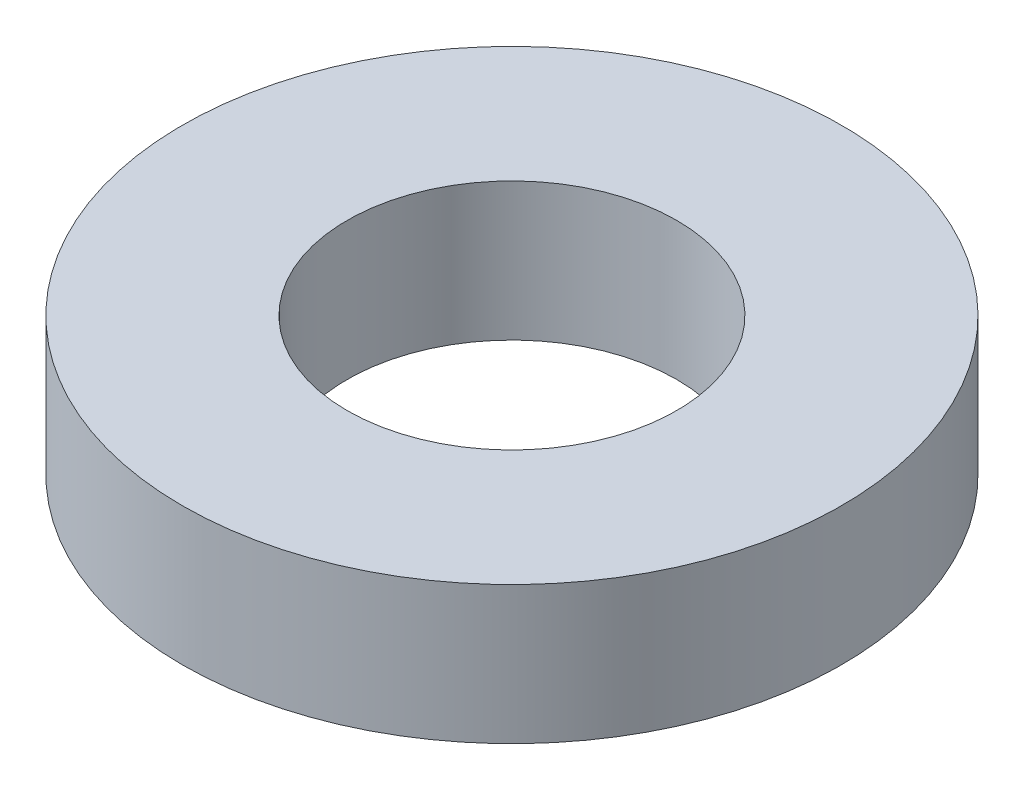
SolidWorks part; units mm, degrees
ref_plane "Front Plane" through (0, 0, 0) normal (0, 0, 1) x (1, 0, 0)
ref_plane "Top Plane" through (0, 0, 0) normal (0, 1, 0) x (1, 0, 0)
ref_plane "Right Plane" through (0, 0, 0) normal (1, 0, 0) x (0, 0, -1)
sketch "Sketch1" plane through (0, 0, 0) normal (0, 1, 0) x (1, 0, 0)
  circle A0 centre (0, 0) radius 55
  dimension "FLANGE_OD" = 110
extrude "Boss-Extrude1" add sketch "Sketch1" along normal blind 23
sketch "Sketch2" plane through (0, 0, 0) normal (0, 1, 0) x (1, 0, 0)
  circle A0 centre (0, 0) radius 27.5
  dimension "BORE_D" = 55
extrude "Cut-Extrude1" cut sketch "Sketch2" along normal through all
sketch "Sketch3" plane through (0, 23, 0) normal (0, 1, 0) x (1, 0, 0)
  circle A0 centre (0, 0) radius 20.6315 construction
  circle A1 centre (-20.6315, 0) radius 3.1533
  dimension "BOLT_D" = 6.3065
  dimension "BOLT_PCD" = 41.2631
extrude "Cut-Extrude2" cut sketch "Sketch3" against normal blind 19.4519 rebuild error yes
pattern_circular "CirPattern1" count 4 over 360 rebuild error yes
